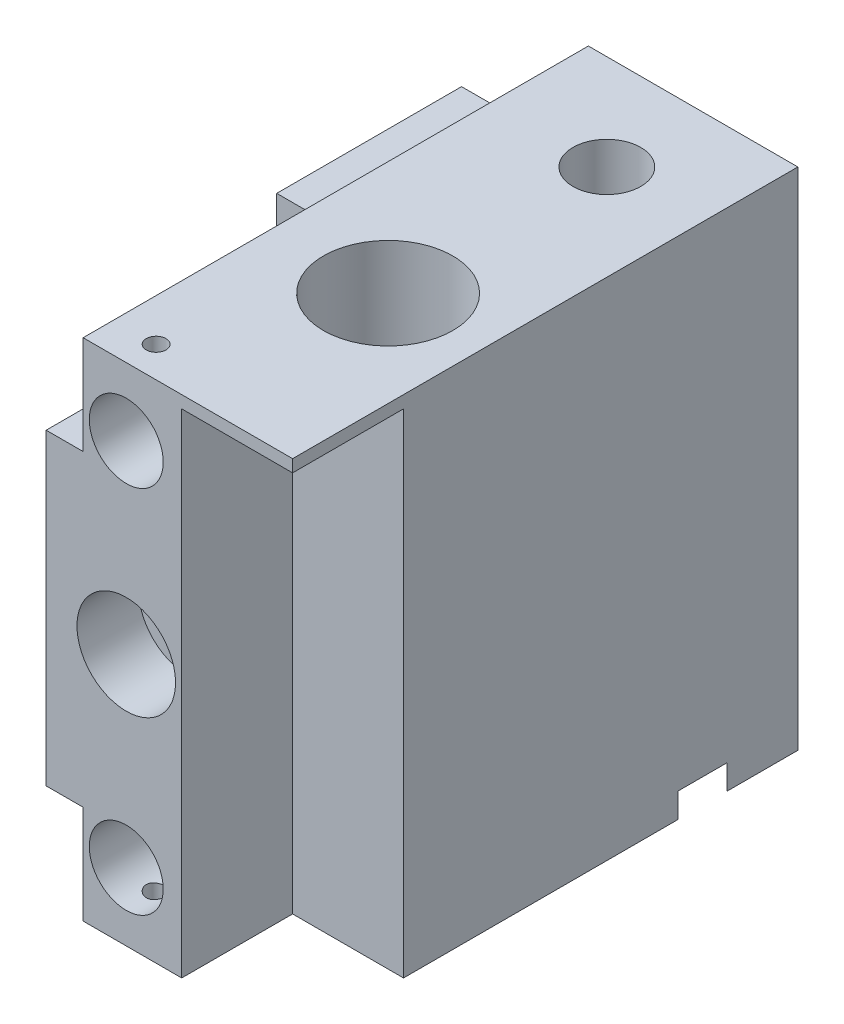
SolidWorks part; units mm, degrees
material "1060 Alloy"
ref_plane "Front Plane" through (0, 0, 0) normal (0, 0, 1) x (1, 0, 0)
ref_plane "Top Plane" through (0, 0, 0) normal (0, 1, 0) x (1, 0, 0)
ref_plane "Right Plane" through (0, 0, 0) normal (1, 0, 0) x (0, 0, -1)
sketch "Sketch1" plane through (0, 0, 0) normal (0, 0, 1) x (1, 0, 0)
  line L0 (-27, -17) -> (-27, -65) construction
  line L1 (0, 0) -> (-40, 0)
  line L2 (0, 0) -> (0, -82)
  line L3 (0, -82) -> (-40, -82)
  line L4 (-40, 0) -> (-40, -82)
  circle A0 centre (-27, -41) radius 5.5
  circle A1 centre (-27, -11) radius 6
  circle A2 centre (-27, -71) radius 6
  dimension "D3" = 11
  dimension "D4" = 12
  dimension "D5" = 12
  dimension "D1" = 40
  dimension "D2" = 82
  dimension "D6" = 11
  dimension "D7" = 30
  dimension "D8" = 13
  dimension "D9" = 30
  dimension "D10" = 11
extrude "Boss-Extrude1" add sketch "Sketch1" along normal blind 12
sketch "Sketch2" plane through (0, 0, 0) normal (0, 0, -1) x (-1, 0, 0)
  line L0 (0, -82) -> (0, 0) construction
  line L1 (40, -82) -> (0, -82) construction
  line L2 (40, 0) -> (40, -82) construction
  line L3 (0, 0) -> (40, 0) construction
  line L4 (0, -82) -> (0, 0)
  line L5 (40, -82) -> (0, -82)
  line L6 (40, 0) -> (40, -82)
  line L7 (0, 0) -> (40, 0)
  circle A0 centre (27, -41) radius 5.5 construction
  circle A1 centre (27, -41) radius 5.5
extrude "Boss-Extrude2" add sketch "Sketch2" along normal blind 70
sketch "Sketch3" plane through (0, 0, 0) normal (0, 1, 0) x (1, 0, 0)
  line L0 (-40, -5) -> (0, -5) construction
  line L1 (-40, -12) -> (-40, 70) construction
  line L2 (0, -12) -> (0, 70) construction
  line L3 (0, -12) -> (-40, -12) construction
  circle A0 centre (-27.1548, -7) radius 1.6
  dimension "D1" = 3.2
  dimension "D2" = 5
  dimension "D3" = 13
extrude "Cut-Extrude1" cut sketch "Sketch3" against normal blind 10
sketch "Sketch4" plane through (0, -82, 0) normal (0, -1, 0) x (1, 0, 0)
  circle A1 centre (-27.1548, 7) radius 1.6
  circle A2 centre (-27.1548, 7) radius 1.6
  dimension "D1" = 0
extrude "Cut-Extrude2" cut sketch "Sketch4" against normal blind 10
sketch "Sketch5" plane through (0, 0, 0) normal (0, 1, 0) x (1, 0, 0)
  line L0 (-15.5, 70) -> (-15.5, 49) construction
  line L1 (-40, 70) -> (0, 70) construction
  line L2 (0, -12) -> (-40, -12) construction
  line L3 (0, -12) -> (0, 70) construction
  line L4 (-15.5, 60) -> (-15.5, 49) construction
  line L5 (-15.5, 29.5) -> (-15.5, 8.5) construction
  line L6 (-15.5, 29.5) -> (-15.5, -12) construction
  circle A1 centre (-15.5, 19) radius 10.5
  circle A2 centre (-15.5, 54.5) radius 5.5
  dimension "D2" = 11
  dimension "D3" = 25
  dimension "D4" = 21
  dimension "D1" = 15.5
  dimension "D6" = 51
extrude "Cut-Extrude3" cut sketch "Sketch5" against normal blind 100
sketch "Sketch6" plane through (0, -82, 0) normal (0, 1, 0) x (1, 0, 0)
  circle A0 centre (-15.5, 54.5) radius 16
  dimension "D1" = 32
extrude "Cut-Extrude4" cut sketch "Sketch6" along normal blind 4
sketch "Sketch19" plane through (0, -78, 0) normal (0, -1, 0) x (-1, 0, 0)
  circle A0 centre (15.5, 54.5) radius 8.05
  dimension "D1" = 16.1
extrude "Cut-Extrude17" cut sketch "Sketch19" against normal blind 16
sketch "Sketch12" plane through (0, -78, 0) normal (0, -1, 0) x (-1, 0, 0)
  line L1 (26.8198, 50.5172) -> (30.8026, 61.837) construction
  line L2 (30.8026, 61.837) -> (19.4828, 65.8198) construction
  line L3 (4.1802, 58.4828) -> (0.1974, 47.163) construction
  line L4 (0.1974, 47.163) -> (11.5172, 43.1802) construction
  circle A0 centre (15.5, 54.5) radius 12 construction
  circle A1 centre (11.5172, 43.1802) radius 1.2
  circle A2 centre (26.8198, 50.5172) radius 1.2
  circle A3 centre (19.4828, 65.8198) radius 1.2
  circle A4 centre (4.1802, 58.4828) radius 1.2
  dimension "D1" = 24
  dimension "D2" = 2.4
extrude "Cut-Extrude12" cut sketch "Sketch12" against normal blind 12
sketch "Sketch13" plane through (0, 0, -70) normal (0, 0, -1) x (-1, 0, 0)
  line L1 (40, 0) -> (60, 0)
  line L2 (40, 0) -> (40, -70)
  line L3 (40, -70) -> (60, -70)
  line L4 (60, 0) -> (60, -70)
  dimension "D1" = 20
  dimension "D2" = 70
extrude "Boss-Extrude3" add sketch "Sketch13" against normal blind 30
sketch "Sketch15" plane through (0, 0, -70) normal (0, 0, -1) x (-1, 0, 0)
  line L0 (34, 0) -> (34, -16)
  line L1 (60, 0) -> (0, 0) construction
  line L2 (34, -16) -> (54.5811, -16)
  line L4 (34, -82) -> (34, -66)
  line L5 (0, -82) -> (11.5314, -82) construction
  line L6 (34, -66) -> (54.5811, -66)
  line L7 (54.5811, -66) -> (54.5811, -16)
  line L8 (34, 0) -> (77.5206, 0)
  line L9 (77.5206, 0) -> (77.5206, -82)
  line L10 (77.5206, -82) -> (34, -82)
  line L11 (60, -70) -> (60, 0) construction
  dimension "D1" = 26
  dimension "D2" = 50
  dimension "D3" = 16
  dimension "D4" = 16
extrude "Cut-Extrude14" cut sketch "Sketch15" against normal blind 115
sketch "Sketch22" plane through (0, -82, 0) normal (0, -1, 0) x (1, 0, 0)
  line L1 (0, 12) -> (-18, 12)
  line L2 (0, 12) -> (0, -6)
  line L3 (0, -6) -> (-18, -6)
  line L4 (-18, 12) -> (-18, -6)
  dimension "D1" = 18
  dimension "D2" = 18
extrude "Cut-Extrude18" cut sketch "Sketch22" against normal blind 80
sketch "Sketch23" plane through (0, 0, 12) normal (0, 0, 1) x (1, 0, 0)
  circle A0 centre (-27, -41) radius 8
  dimension "D1" = 16
extrude "Cut-Extrude19" cut sketch "Sketch23" against normal blind 10
sketch "Sketch24" plane through (0, 0, -70) normal (0, 0, -1) x (-1, 0, 0)
  circle A0 centre (27, -41) radius 10
extrude "Cut-Extrude20" cut sketch "Sketch24" against normal blind 2
